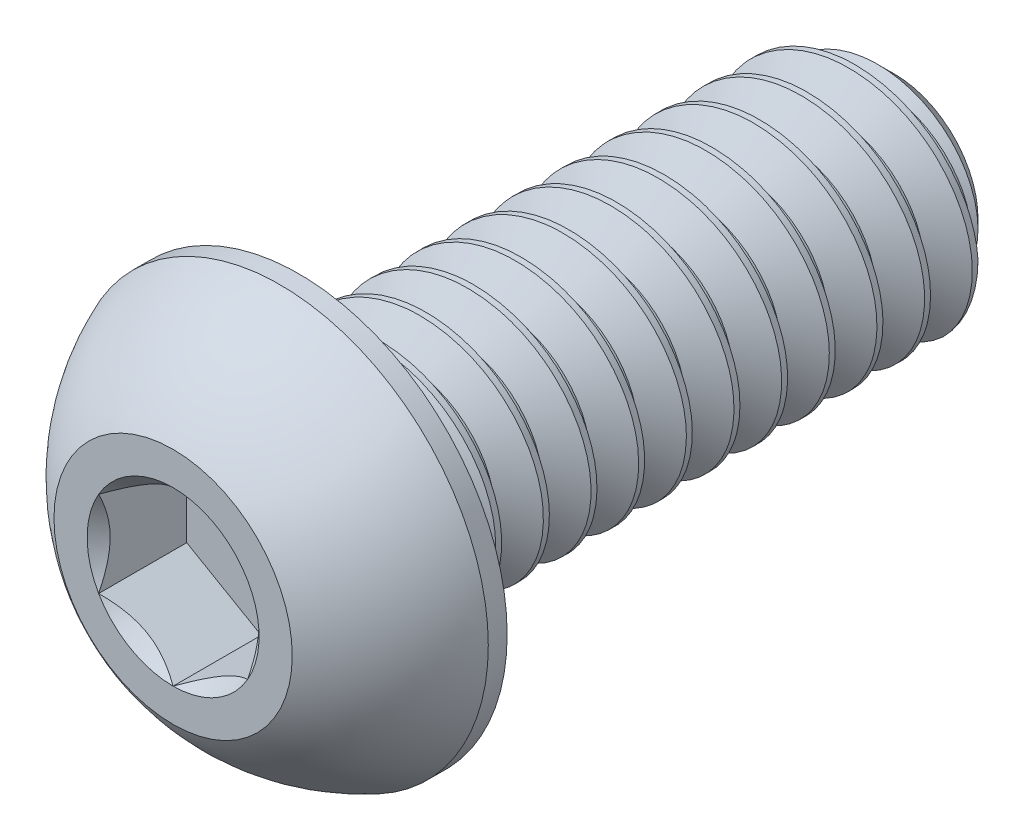
SolidWorks part; units mm, degrees
material "Plain Carbon Steel"
ref_plane "Front" through (0, 0, 0) normal (0, 0, 1) x (1, 0, 0)
ref_plane "Top" through (0, 0, 0) normal (0, 1, 0) x (1, 0, 0)
ref_plane "Right" through (0, 0, 0) normal (1, 0, 0) x (0, 0, -1)
sketch "Sketch1" plane through (0, 0, 0) normal (1, 0, 0) x (0, 0, -1)
  line L2 (3.3528, 3.175) -> (19.2278, 3.175)
  line L3 (19.2278, 3.175) -> (19.2278, 0)
  line L4 (19.2278, 0) -> (3.3528, 0)
  line L6 (2.8499, 5.5499) -> (3.3528, 5.5499) construction
  line L7 (19.2278, 3.175) -> (19.2278, -3.175) construction
  line L8 (0, 0) -> (3.3528, 0) construction
  line L9 (3.3528, 5.5499) -> (3.3528, -5.5499) construction
  line L11 (3.3528, 3.175) -> (3.3528, 0)
  line L13 (0, 1.9844) -> (0, -1.9844) construction
  line L14 (0, 1.9844) -> (0, 3.175) construction
  arc A3 (0, 3.175) -> (2.8499, 5.5499) centre (5.0603, 0) cw construction
  dimension "D1" = 0.5029
  dimension "Head Ht" = 3.3528
  dimension "Head Dia" = 11.0998
  dimension "Dia" = 6.35
  dimension "Lg" = 15.875
  dimension "Hex" = 3.9688
revolve "Revolve1" add sketch "Sketch1" angle 360 mid plane about L4
sketch "Sketch3" plane through (0, 0, -19.2278) normal (0, 0, -1) x (-1, 0, 0)
  circle A0 centre (0, 0) radius 3.175
curve "Helix/Spiral1" pitch 1.27 height 17.145 radius 3.175 centre (0, 0, -19.2278) axis (0, 0, 1) start towards (0, 1, 0)
sketch "Sketch2" plane through (0, 0, 0) normal (1, 0, 0) x (0, 0, -1)
  line L0 (19.2278, 3.175) -> (20.339, 3.175)
  line L1 (20.339, 3.175) -> (19.8628, 2.3501)
  line L2 (19.8628, 2.3501) -> (19.704, 2.3501)
  line L3 (19.704, 2.3501) -> (19.2278, 3.175)
  line L4 (19.4659, 2.7626) -> (20.1009, 2.7626) construction
  dimension "D1" = 60
  dimension "D2" = 0.1588
  dimension "D3" = 0.635
chamfer "Chamfer1" distance 0.9525 angle 45 1 edges at (0, 3.175, -19.2278)
sweep "Cut-Sweep1" cut profiles "Sketch2" path "Helix/Spiral1"
sketch "Sketch7" plane through (0, 0, 0) normal (1, 0, 0) x (0, 0, -1)
  line L6 (2.8499, 5.5499) -> (3.3528, 5.5499) construction
  line L8 (0, 0) -> (3.3528, 0) construction
  line L11 (3.3528, 5.5499) -> (3.3528, -5.5499) construction
  line L12 (2.8499, 5.5499) -> (3.3528, 5.5499)
  line L13 (0, 0) -> (3.3528, 0)
  line L14 (0, 1.9844) -> (0, -1.9844) construction
  line L15 (3.3528, 5.5499) -> (3.3528, 0)
  line L16 (0, 3.175) -> (0, 0)
  arc A2 (2.8499, 5.5499) -> (0, 3.175) centre (5.0603, 0) ccw construction
  arc A3 (2.8499, 5.5499) -> (0, 3.175) centre (5.0603, 0) ccw
revolve "Revolve2" add sketch "Sketch7" angle 360 mid plane about L13
sketch "Sketch5" plane through (0, 0, 0) normal (0, 0, 1) x (1, 0, 0)
  line L1 (1.9844, -1.1457) -> (1.9844, 1.1457)
  line L2 (1.9844, 1.1457) -> (0, 2.2914)
  line L3 (0, 2.2914) -> (-1.9844, 1.1457)
  line L4 (-1.9844, 1.1457) -> (-1.9844, -1.1457)
  line L5 (-1.9844, -1.1457) -> (0, -2.2914)
  line L6 (0, -2.2914) -> (1.9844, -1.1457)
  circle A0 centre (0, 0) radius 1.9844 construction
extrude "Cut-Extrude2" cut sketch "Sketch5" against normal blind 2.347
sketch "Sketch6" plane through (0, 0, 0) normal (0, 0, 1) x (1, 0, 0)
  circle A0 centre (0, 0) radius 2.2914
extrude "Cut-Extrude3" cut sketch "Sketch6" against normal blind 2.347 draft 45
sketch "Sketch9" [suppressed] plane through (0, 0, -3.3528) normal (0, 0, 1) x (1, 0, 0)
  circle A2 centre (0, 0) radius 3.175
extrude "Boss-Extrude2" [suppressed] add sketch "Sketch9" against normal offset from surface (12.7 mm away) 22.225
sketch "Sketch10" plane through (0, 0, 0) normal (1, 0, 0) x (0, 0, -1)
  line L0 (19.2278, 3.175) -> (19.2278, -3.175) construction
  point P0 (17.3228, -3.175)
  dimension "D1" = 1.905
equation "\"D3@Helix/Spiral1\" = \"Lg@Sketch1\" + \"D4@Helix/Spiral1\""
equation "\"D2@Sketch2\" = \"D4@Helix/Spiral1\" * .125"
equation "\"D3@Sketch2\" = \"D4@Helix/Spiral1\" * .5"
equation "\"D1@Chamfer1\" = \"D4@Helix/Spiral1\" * .75"
equation "\"D1@Cut-Extrude2\" = \"Head Ht@Sketch1\" * .7"
equation "\"D1@Sketch1\" = \"Head Ht@Sketch1\" * .15"
equation "\"D1@Sketch10\" = \"D4@Helix/Spiral1\" * 1.5"
equation "\"D1@Cut-Extrude3\" = \"D1@Cut-Extrude2\""
